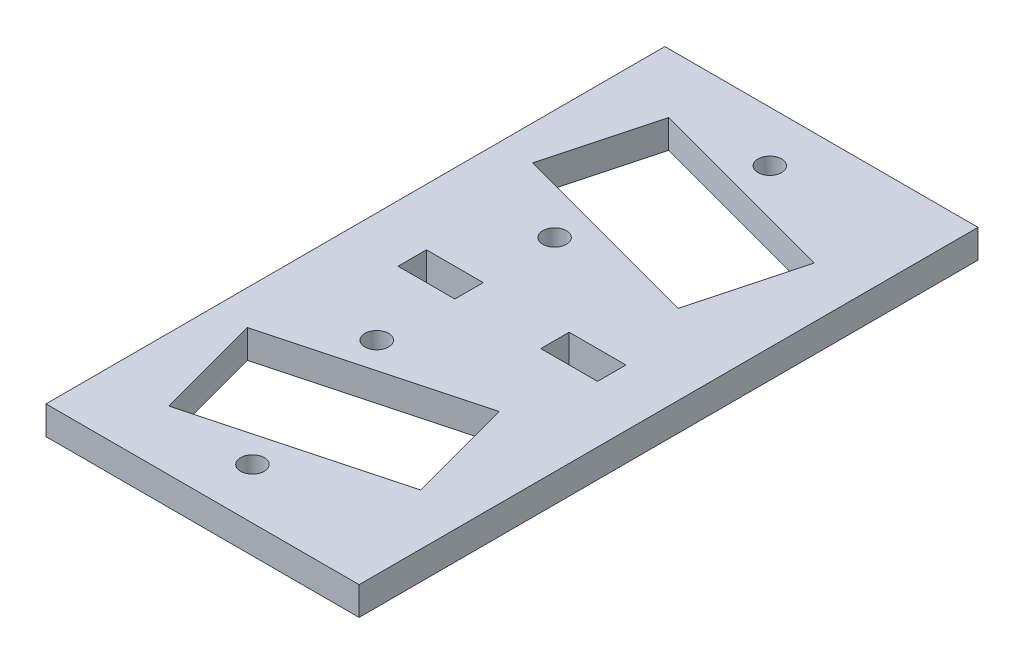
SolidWorks part; units mm, degrees
ref_plane "Front Plane" through (0, 0, 0) normal (0, 0, 1) x (1, 0, 0)
ref_plane "Top Plane" through (0, 0, 0) normal (0, 1, 0) x (1, 0, 0)
ref_plane "Right Plane" through (0, 0, 0) normal (1, 0, 0) x (0, 0, -1)
sketch "Sketch1" plane through (0, 0, 0) normal (0, 1, 0) x (1, 0, 0)
  line L0 (240.7757, 11.1461) -> (262.992, 5.1932)
  line L1 (236.9075, 29.7812) -> (271.9075, 29.7812)
  line L2 (236.9075, 29.7812) -> (236.9075, -39.3947)
  line L3 (236.9075, -39.3947) -> (271.9075, -39.3947)
  line L4 (271.9075, 29.7812) -> (271.9075, -39.3947)
  line L5 (240.7757, 11.1461) -> (243.985, 23.1235)
  line L6 (262.992, 5.1932) -> (266.2013, 17.1707)
  line L7 (243.985, 23.1235) -> (266.2013, 17.1707)
  line L8 (253.0312, 24.4501) -> (255.5904, 23.7642) construction
  line L9 (252.1737, 16.1327) -> (251.4878, 13.5732) construction
  line L10 (242.3803, 17.1348) -> (264.5966, 11.182) construction
  line L11 (236.9075, -4.8068) -> (271.9075, -4.8068) construction
  line L12 (242.3803, -26.7484) -> (264.5966, -20.7955) construction
  line L13 (252.1737, -25.7463) -> (251.4878, -23.1868) construction
  line L14 (253.0312, -34.0636) -> (255.5904, -33.3778) construction
  line L15 (262.992, -14.8068) -> (266.2013, -26.7843)
  line L16 (240.7757, -20.7596) -> (262.992, -14.8068)
  line L17 (243.985, -32.7371) -> (240.7757, -20.7596)
  line L18 (266.2013, -26.7843) -> (243.985, -32.7371)
  line L20 (243.2575, -6.3943) -> (249.6075, -6.3943)
  line L21 (243.2575, -6.3943) -> (243.2575, -3.2193)
  line L22 (243.2575, -3.2193) -> (249.6075, -3.2193)
  line L23 (249.6075, -6.3943) -> (249.6075, -3.2193)
  line L24 (243.2575, -6.3943) -> (249.6075, -3.2193) construction
  line L25 (243.2575, -3.2193) -> (249.6075, -6.3943) construction
  line L26 (259.2075, -6.3943) -> (265.5575, -6.3943)
  line L27 (259.2075, -6.3943) -> (259.2075, -3.2193)
  line L28 (259.2075, -3.2193) -> (265.5575, -3.2193)
  line L29 (265.5575, -6.3943) -> (265.5575, -3.2193)
  line L30 (259.2075, -6.3943) -> (265.5575, -3.2193) construction
  line L31 (259.2075, -3.2193) -> (265.5575, -6.3943) construction
  circle A0 centre (254.3108, 24.1071) radius 1.3248
  circle A1 centre (249.2262, 5.1313) radius 1.3248
  circle A2 centre (249.2262, -14.7449) radius 1.3248
  circle A3 centre (254.3108, -33.7207) radius 1.3248
  point P26 (246.4325, -4.8068)
  point P31 (262.3825, -4.8068)
  dimension "D1" = 10
  dimension "D2" = 3.175
  dimension "D3" = 3.175
  dimension "D4" = 6.35
  dimension "D5" = 6.35
  dimension "D6" = 6.35
  dimension "D7" = 6.35
  dimension "D8" = 35
extrude "Boss-Extrude1" add sketch "Sketch1" along normal blind 3.175
